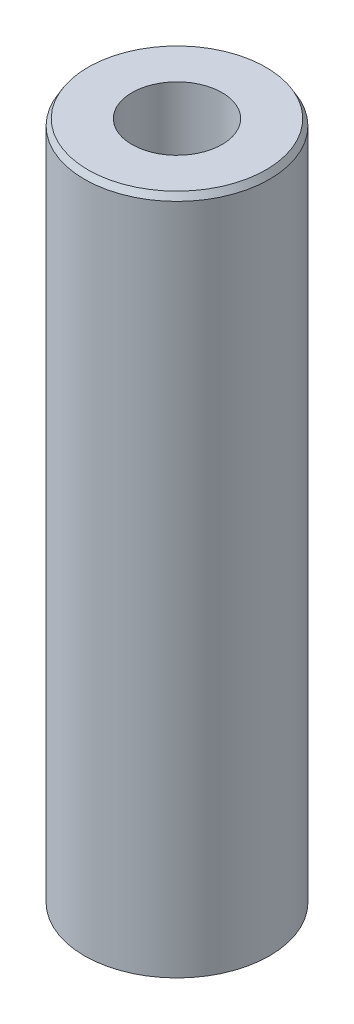
SolidWorks part; units mm, degrees
ref_plane "Front Plane" through (0, 0, 0) normal (0, 0, 1) x (1, 0, 0)
ref_plane "Top Plane" through (0, 0, 0) normal (0, 1, 0) x (1, 0, 0)
ref_plane "Right Plane" through (0, 0, 0) normal (1, 0, 0) x (0, 0, -1)
sketch "Sketch1" plane through (0, 0, 0) normal (0, 1, 0) x (1, 0, 0)
  circle A0 centre (0, 0) radius 10
  dimension "SHAFT_OD" = 20
extrude "Boss-Extrude1" add sketch "Sketch1" along normal blind 73.7155
sketch "Sketch2" plane through (0, 0, 0) normal (0, 1, 0) x (1, 0, 0)
  circle A0 centre (0, 0) radius 4.8637
  dimension "BORE_D" = 9.7274
extrude "Cut-Extrude1" cut sketch "Sketch2" along normal through all
chamfer "Chamfer1" distance 0.6802 angle 30 2 edges at (0, 73.7155, 10) (0, 0, 10) first distance on face at (0, 73.7155, 10) first distance on face at (0, 0, 4.8637)
